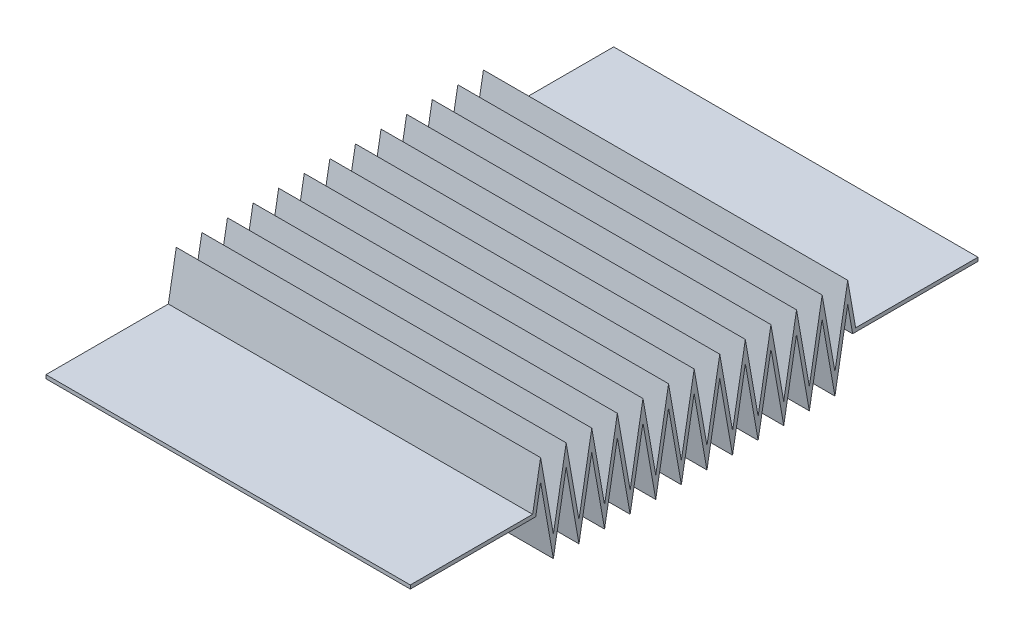
SolidWorks part; units mm, degrees
ref_plane "Front Plane" through (0, 0, 0) normal (0, 0, 1) x (1, 0, 0)
ref_plane "Top Plane" through (0, 0, 0) normal (0, 1, 0) x (1, 0, 0)
ref_plane "Right Plane" through (0, 0, 0) normal (1, 0, 0) x (0, 0, -1)
sketch "Sketch2" plane through (0, 0, 0) normal (0, 0, 1) x (1, 0, 0)
  line L1 (-27.5, 10) -> (27.5, 10)
  line L2 (-27.5, 10) -> (-27.5, 0)
  line L3 (-27.5, 0) -> (27.5, 0)
  line L4 (27.5, 10) -> (27.5, 0)
  point P4 (0, 0)
  dimension "D1" = 10
  dimension "D2" = 55
sketch "Sketch3" plane through (0, 0, 0) normal (1, 0, 0) x (0, 0, -1)
  line L0 (0, 10) -> (77.9132, 10) construction
  line L1 (0, 0) -> (77.9132, 0) construction
  line L2 (77.9132, 2.25) -> (77.9132, -15.75) construction
  line L3 (17, 5) -> (17.8783, 10)
  line L4 (17.8783, 10) -> (19.6348, 0)
  line L5 (19.6348, 0) -> (21.3913, 10)
  line L6 (21.3913, 10) -> (23.1478, 0)
  line L7 (23.1478, 0) -> (24.9044, 10)
  line L8 (24.9044, 10) -> (26.6609, 0)
  line L9 (26.6609, 0) -> (28.4174, 10)
  line L10 (28.4174, 10) -> (30.174, 0)
  line L11 (30.174, 0) -> (31.9305, 10)
  line L12 (31.9305, 10) -> (33.687, 0)
  line L13 (33.687, 0) -> (35.4435, 10)
  line L14 (35.4435, 10) -> (37.2001, 0)
  line L15 (37.2001, 0) -> (38.9566, 10)
  line L16 (38.9566, 10) -> (40.7131, 0)
  line L17 (40.7131, 0) -> (42.4697, 10)
  line L18 (42.4697, 10) -> (44.2262, 0)
  line L19 (0, 10) -> (0, 0) construction
  line L20 (44.2262, 0) -> (45.9827, 10)
  line L21 (45.9827, 10) -> (47.7392, 0)
  line L22 (47.7392, 0) -> (49.4958, 10)
  line L23 (49.4958, 10) -> (51.2523, 0)
  line L24 (51.2523, 0) -> (53.0088, 10)
  line L25 (53.0088, 10) -> (54.7654, 0)
  line L26 (54.7654, 0) -> (56.5219, 10)
  line L27 (56.5219, 10) -> (58.2784, 0)
  line L28 (58.2784, 0) -> (60.0349, 10)
  line L29 (60.0349, 10) -> (60.9132, 5)
  line L30 (77.9132, 10) -> (77.9132, 0) construction
  line L31 (17, 5) -> (0, 5)
  line L32 (60.9132, 5) -> (77.9132, 5)
  dimension "D2" = 17
  dimension "D1" = 10
  dimension "D3" = 17
extrude "Extrude-Thin1" add sketch "Sketch3" against normal mid plane 50 thin thin type mid plane wall 0.5
